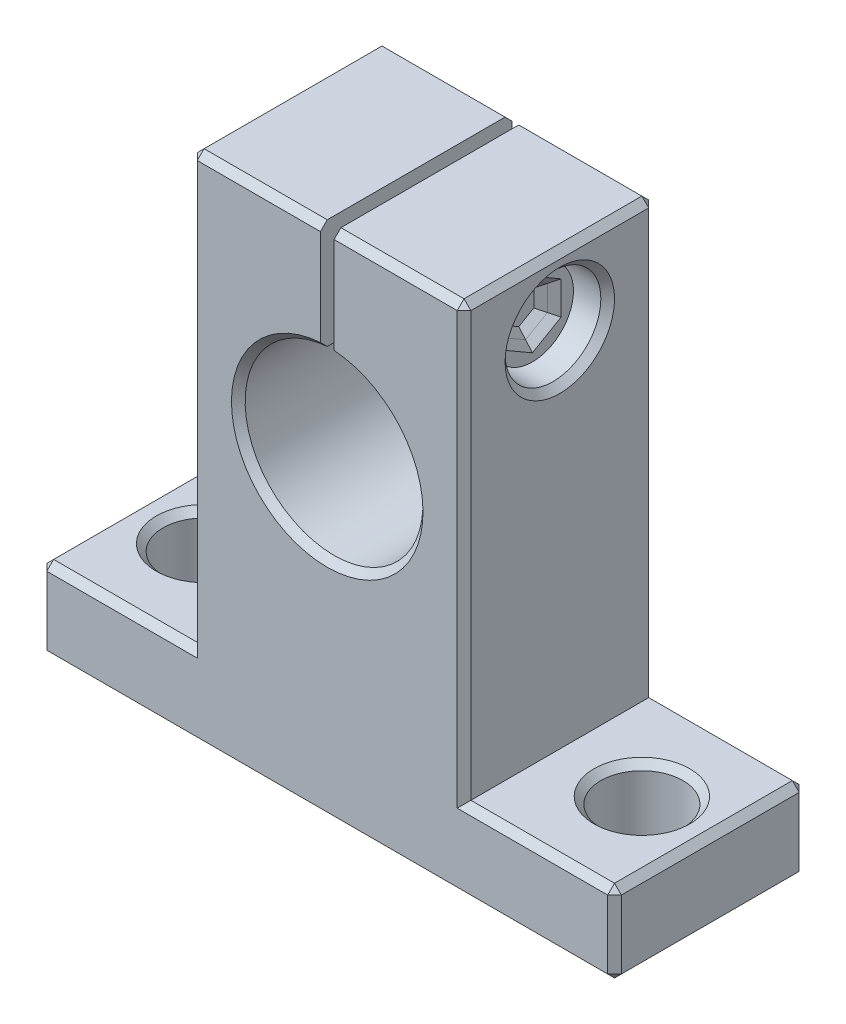
SolidWorks part; units mm, degrees
material "3.0205 (EN-AW 1200)"
ref_plane "前视基准面" through (0, 0, 0) normal (0, 0, 1) x (1, 0, 0)
ref_plane "上视基准面" through (0, 0, 0) normal (0, 1, 0) x (1, 0, 0)
ref_plane "右视基准面" through (0, 0, 0) normal (1, 0, 0) x (0, 0, -1)
sketch "草图1" plane through (0, 0, 0) normal (0, 1, 0) x (1, 0, 0)
  line L0 (5, 7) -> (37, 7) construction
  line L1 (0, 0) -> (42, 0)
  line L2 (0, 0) -> (0, 14)
  line L3 (0, 14) -> (42, 14)
  line L4 (42, 0) -> (42, 14)
  line L5 (21, 14) -> (21, 0) construction
  circle A0 centre (5, 7) radius 3
  circle A1 centre (37, 7) radius 3
  dimension "D3" = 6
  dimension "D4" = 6
  dimension "D1" = 42
  dimension "D2" = 14
extrude "凸台-拉伸1" add sketch "草图1" along normal blind 6
sketch "草图2" plane through (0, 6, 0) normal (0, 1, 0) x (1, 0, 0)
  line L0 (21, 14) -> (21, 0) construction
  line L1 (42, 14) -> (0, 14) construction
  line L2 (0, 0) -> (42, 0) construction
  line L3 (11, 14) -> (11, 0)
  line L4 (31, 14) -> (31, 0)
  line L5 (11, 14) -> (31, 14)
  line L6 (11, 0) -> (31, 0)
  dimension "D1" = 10
  dimension "D2" = 10
extrude "凸台-拉伸2" add sketch "草图2" along normal blind 31.5
sketch "草图3" plane through (0, 0, 0) normal (0, 0, 1) x (1, 0, 0)
  line L0 (11, 16.5) -> (31, 16.5) construction
  line L1 (0, 0) -> (42, 0) construction
  line L2 (11, 29.5) -> (20.5, 29.5) construction
  line L5 (-5.4667, 29.5) -> (50.6794, 29.5) construction
  line L8 (21.5, 29.4807) -> (21.5, 37.5)
  line L9 (20.5, 29.4807) -> (20.5, 37.5)
  line L10 (-5.4667, 16.5) -> (50.6794, 16.5) construction
  line L14 (20.5, 37.5) -> (21.5, 37.5)
  line L15 (21.5, 29.5) -> (31, 29.5) construction
  arc A0 (20.5, 29.4807) -> (21.5, 29.4807) centre (21, 23) ccw
  dimension "D1" = 16.5
  dimension "D2" = 13
extrude "切除-拉伸1" cut sketch "草图3" against normal blind 37.5
sketch "草图5" plane through (31, 0, 0) normal (1, 0, 0) x (0, 0, -1)
  line L1 (7, 37.5) -> (7, 32.5) construction
  line L2 (0, 37.5) -> (14, 37.5) construction
  line L3 (0, 32.5) -> (14, 32.5) construction
  circle A0 centre (7, 32.5) radius 3.5
  dimension "D1" = 7
extrude "切除-拉伸2" cut sketch "草图5" against normal blind 2
sketch "草图6" plane through (29, 0, 0) normal (1, 0, 0) x (0, 0, -1)
  line L0 (7, 35.5) -> (7, 29.5) construction
  line L1 (4.4019, 34) -> (9.5981, 31) construction
  line L2 (4.4019, 31) -> (9.5981, 34) construction
  line L9 (5.4019, 33.4226) -> (7, 34.3453)
  line L10 (7, 34.3453) -> (8.5981, 33.4226)
  line L11 (8.5981, 33.4226) -> (8.5981, 31.5774)
  line L12 (8.5981, 31.5774) -> (7, 30.6547)
  line L13 (7, 30.6547) -> (5.4019, 31.5774)
  line L14 (5.4019, 31.5774) -> (5.4019, 33.4226)
  circle A0 centre (7, 32.5) radius 3
  circle A1 centre (7, 32.5) radius 3.5
  circle M1 centre (7, 32.5) radius 3.5
  dimension "D1" = 60
  dimension "D2" = 60
extrude "切除-拉伸3" cut sketch "草图6" against normal blind 1 contours L14 L13 L12 L11 L10 L9 | A0 M1 region at (29, 32.5, -7) region at (29, 32.5, -3.599)
sketch "草图7" plane through (11, 0, 0) normal (-1, 0, 0) x (0, 0, 1)
  circle A0 centre (-7, 32.5) radius 1.5
extrude "凸台-拉伸3" add sketch "草图7" along normal blind 1 and the other way blind 15
sketch "草图8" plane through (11, 0, 0) normal (-1, 0, 0) x (0, 0, 1)
  circle A0 centre (-7, 32.5) radius 1.8
  circle A1 centre (-7, 32.5) radius 1.5
extrude "切除-拉伸4" cut sketch "草图8" against normal blind 0.5
chamfer "倒角1" distance 0.5 angle 45 1 edges at (11, 32.5, -5.2)
chamfer "倒角2" distance 0.5 angle 45 1 edges at (31, 32.5, -10.5)
chamfer "倒角3" distance 0.5 angle 45 12 edges at (29, 31.116, -7.799) (29, 32.5, -8.5981) (29, 33.884, -7.799) (29, 33.884, -6.201) (29, 32.5, -5.4019) (29, 31.116, -6.201) (28, 33.884, -6.201) (28, 33.884, -7.799) (28, 32.5, -8.5981) (28, 31.116, -7.799) (28, 31.116, -6.201) (28, 32.5, -5.4019)
chamfer "倒角4" distance 0.5 angle 45 30 edges at (21, 16.5, 0) (21, 16.5, -14) (0, 0, -7) (0, 6, -7) (11, 37.5, -7) (31, 37.5, -7) (42, 6, -7) (15.75, 37.5, 0) (0, 3, 0) (21, 0, 0) (26.25, 37.5, 0) (42, 3, 0) (42, 0, -7) (26.25, 37.5, -14) (42, 3, -14) (21, 0, -14) (0, 3, -14) (15.75, 37.5, -14) (37, 0, -4) (37, 6, -4) (5, 0, -4) (5, 6, -4)
